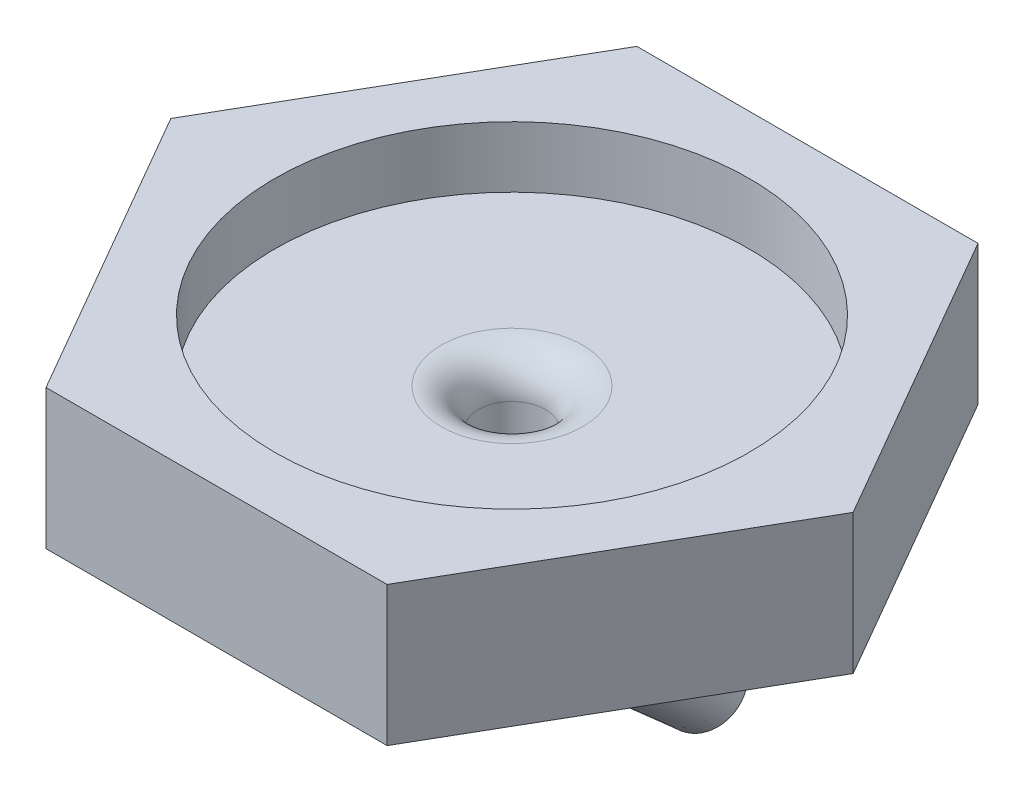
SolidWorks part; units mm, degrees
ref_plane "Front Plane" through (0, 0, 0) normal (0, 0, 1) x (1, 0, 0)
ref_plane "Top Plane" through (0, 0, 0) normal (0, 1, 0) x (1, 0, 0)
ref_plane "Right Plane" through (0, 0, 0) normal (1, 0, 0) x (0, 0, -1)
sketch "Sketch11" plane through (0, 0, 0) normal (0, 1, 0) x (1, 0, 0)
  line L7 (18.3309, 0) -> (9.1654, 15.875)
  line L8 (9.1654, 15.875) -> (-9.1654, 15.875)
  line L9 (-9.1654, 15.875) -> (-18.3309, 0)
  line L10 (-18.3309, 0) -> (-9.1654, -15.875)
  line L11 (-9.1654, -15.875) -> (9.1654, -15.875)
  line L12 (9.1654, -15.875) -> (18.3309, 0)
  circle A0 centre (0, 0) radius 15.875 construction
  dimension "D1" = 31.75
extrude "MainHolder" add sketch "Sketch11" along normal blind 7.5
sketch "Sketch12" plane through (0, 7.5, 0) normal (0, 1, 0) x (1, 0, 0)
  circle A0 centre (0, 0) radius 12.75
  dimension "D1" = 25.5
extrude "MagnetCutout" cut sketch "Sketch12" against normal blind 3.28
sketch "Sketch13" plane through (0, 4.22, 0) normal (0, 1, 0) x (1, 0, 0)
  circle A0 centre (0, 0) radius 1.8
  dimension "D1" = 3.6
extrude "MagnetHole" cut sketch "Sketch13" against normal up to next
sketch "DrainPath" plane through (0, 0, 0) normal (1, 0, 0) x (0, 0, -1)
  line L0 (0, 0) -> (0, -2)
  line L1 (1.7574, -6.2426) -> (10.2426, -14.7279)
  arc A0 (1.7574, -6.2426) -> (0, -2) centre (6, -2) cw
  point P7 (0, -4.4853)
  dimension "D3" = 6
  dimension "D1" = 135
  dimension "D2" = 12
  dimension "D4" = 2
sketch "DrainOpening" plane through (0, 0, 0) normal (0, -1, 0) x (1, 0, 0)
  circle A0 centre (0, 0) radius 1.125
  circle A2 centre (0, 0) radius 2
  dimension "D1" = 2.25
  dimension "D2" = 4
sweep "Drain" add profiles "DrainOpening" path "DrainPath"
ref_axis "DrainOutAxis" through (0, -5.4471, -0.9619) along (0, -0.7071, -0.7071)
ref_plane "DrainMidPlain" through (0, 0, 0) normal (-1, 0, 0) x (0, -0.7071, -0.7071)
sketch "BarbOutline" plane through (0, 0, 0) normal (-1, 0, 0) x (0, -0.7071, -0.7071)
  line L0 (17.6569, 1.1716) -> (11.6569, 1.1716)
  line L1 (11.6569, 1.1716) -> (11.6569, 0.7966)
  line L2 (11.6569, 0.7966) -> (17.6569, 1.1716)
  line L3 (5.6569, 1.1716) -> (17.6569, 1.1716) construction
  line L4 (4.5319, 3.1716) -> (18.7819, 3.1716) construction
  line L8 (5.6569, 1.1716) -> (17.6569, 1.1716) construction
  dimension "D1" = 6
  dimension "D2" = 2.375
revolve "Barb" add sketch "BarbOutline" angle 360 about axis through (0, -5.4471, -0.9619) along (0, -0.7071, -0.7071)
ref_axis "MagnetAxis" through (0, 0, 0) along (0, 1, 0)
fillet "DrainBaseFillet" radius 2 1 edges at (0, 4.22, 1.8) type face fillet first side face at (0, 4.22, 1.8) second side face at (0, 4.22, 1.8)
fillet "DrainBottomFillet" radius 2 1 edges at (0, 0, -2) type face fillet first side face at (0, 0, -2) second side face at (0, -2, -2)
fillet "BarbFillet" radius 1 1 edges at (0, -11.8995, -4.5858)
equation "\"channel_diameter\"= 4mm"
equation "\"channel_length\"= 12mm"
equation "\"barb_length\"= 6mm"
equation "\"lumen_diameter\"= 2.25mm"
equation "\"magnet_holder_thickness\"= 7.5"
equation "\"magnet_diameter\"=25.4"
equation "\"magnet_holder_tolerance\"= 0.1mm"
equation "\"magnet_thickness\"= 3.18mm"
equation "\"D1@Sketch11\"=\"magnet_diameter\" * 1.25"
equation "\"D1@MainHolder\" = \"magnet_holder_thickness\""
equation "\"D1@Sketch12\"=\"magnet_diameter\" + \"magnet_holder_tolerance\""
equation "\"D1@MagnetCutout\" = \"magnet_thickness\" + \"magnet_holder_tolerance\""
equation "\"magnet_hole_small\"= 4.83mm"
equation "\"D1@Sketch13\"=\"channel_diameter\" * 0.9"
equation "\"drain_angle\"= 135"
equation "\"D1@DrainPath\" = \"drain_angle\""
equation "\"D2@DrainPath\" = \"barb_length\" * 2"
equation "\"D1@DrainOpening\" = \"lumen_diameter\""
equation "\"D1@BarbOutline\" = \"barb_length\""
equation "\"D2@BarbOutline\"=\"channel_diameter\" / 2 + \"barb_extension\""
equation "\"FilletBase\"=3"
equation "\"barb_extension\"= 0.75mm / 2"
equation "\"D2@DrainOpening\"=\"channel_diameter\""
